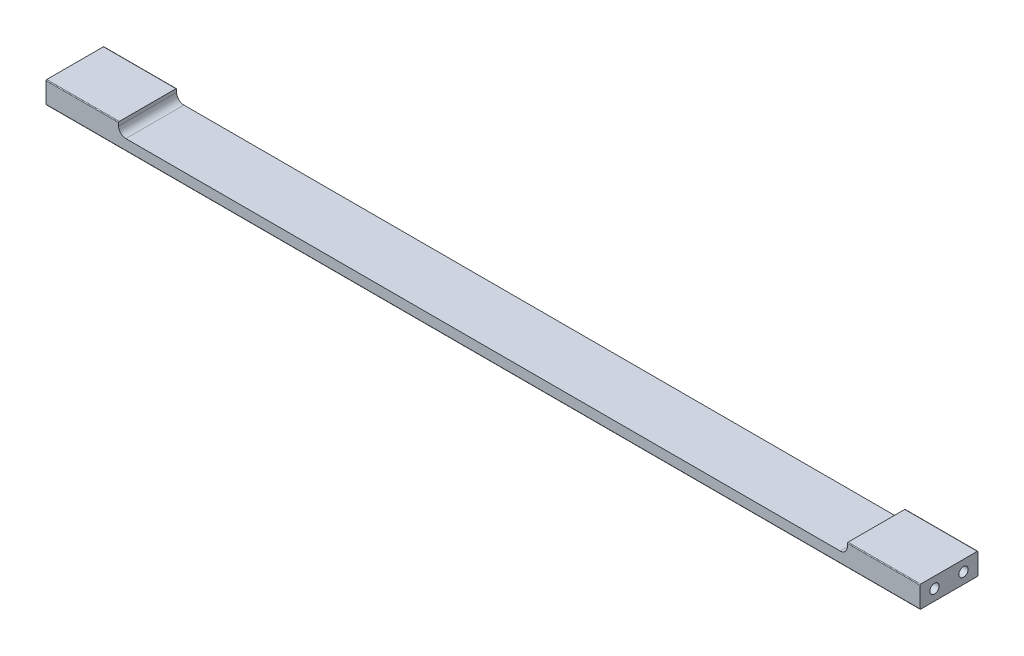
SolidWorks part; units mm, degrees
ref_plane "Front Plane" through (0, 0, 0) normal (0, 0, 1) x (1, 0, 0)
ref_plane "Top Plane" through (0, 0, 0) normal (0, 1, 0) x (1, 0, 0)
ref_plane "Right Plane" through (0, 0, 0) normal (1, 0, 0) x (0, 0, -1)
sketch "Sketch1" plane through (0, 0, 0) normal (0, 1, 0) x (1, 0, 0)
  line L1 (191.135, -12.7) -> (-191.135, -12.7)
  line L2 (191.135, -12.7) -> (191.135, 12.7)
  line L3 (191.135, 12.7) -> (-191.135, 12.7)
  line L4 (-191.135, -12.7) -> (-191.135, 12.7)
  line L5 (191.135, -12.7) -> (-191.135, 12.7) construction
  line L6 (191.135, 12.7) -> (-191.135, -12.7) construction
  point P0 (0, 0)
  dimension "Length" = 382.27
  dimension "Width" = 25.4
sketch "Sketch2" plane through (0, 0, 0) normal (1, 0, 0) x (0, 0, -1)
  line L0 (12.7, 4.7625) -> (12.7, -4.7625) construction
  point P2 (12.7, 0)
  dimension "Thickness" = 9.525
sketch "Sketch3" plane through (0, 0, 0) normal (0, 1, 0) x (1, 0, 0)
  line L1 (-191.135, 12.7) -> (191.135, 12.7)
  line L2 (-191.135, 12.7) -> (-191.135, -12.7)
  line L3 (-191.135, -12.7) -> (191.135, -12.7)
  line L4 (191.135, 12.7) -> (191.135, -12.7)
extrude "Boss-Extrude1" add sketch "Sketch3" against normal up to vertex (4.7625 mm away) and the other way up to vertex (4.7625 mm away) up to point (0, -4.7625, -12.7) other way up to point (0, 4.7625, -12.7)
fillet "Fillet1" radius 0.3143 4 edges at (0, -4.7625, 12.7) (0, -4.7625, -12.7) (0, 4.7625, -12.7) (0, 4.7625, 12.7)
sketch "Sketch4" plane through (-191.135, 0, 0) normal (-1, 0, 0) x (0, 0, 1)
  line L0 (0, 0) -> (6.35, 0) construction
  line L1 (0, 0) -> (-6.35, 0) construction
hole_wizard "Tap Drill for #10-32 Tap1" positions "Sketch5" profile "Sketch6" hole size "#10-32" standard "ANSI Inch"
sketch "Sketch5" plane through (-191.135, 0, 0) normal (-1, 0, 0) x (0, 0, 1)
  point P0 (-6.35, 0)
  point P3 (6.35, 0)
sketch "Sketch6" plane through (-191.135, 0, -6.35) normal (0, 1, 0) x (0, 0, 1)
  line L0 (0, 0) -> (0, 26.6133)
  line L1 (0, 26.6133) -> (2.0193, 25.4)
  line L2 (2.0193, 25.4) -> (2.0193, 0)
  line L5 (2.0193, 0) -> (0, 0)
  line L10 (0, 26.6133) -> (-2.0193, 25.4) construction
  line L11 (0, -6.35) -> (0, 107.95) construction
  dimension "Hole Dia." = 4.0386
  dimension "Hole Depth" = 25.4
  dimension "Drill Angle" = 118
hole_wizard "Tap Drill for #10-32 Tap2" positions "Sketch7" profile "Sketch8" hole size "#10-32" standard "ANSI Inch"
sketch "Sketch7" plane through (191.135, 0, 0) normal (1, 0, 0) x (0, 0, -1)
  point P0 (-6.35, 0)
  point P3 (6.35, 0)
sketch "Sketch8" plane through (191.135, 0, 6.35) normal (0, 1, 0) x (0, 0, -1)
  line L0 (0, 0) -> (0, 26.6133)
  line L1 (0, 26.6133) -> (2.0193, 25.4)
  line L2 (2.0193, 25.4) -> (2.0193, 0)
  line L5 (2.0193, 0) -> (0, 0)
  line L10 (0, 26.6133) -> (-2.0193, 25.4) construction
  line L11 (0, -6.35) -> (0, 107.95) construction
  dimension "Hole Dia." = 4.0386
  dimension "Hole Depth" = 25.4
  dimension "Drill Angle" = 118
sketch "Sketch9" plane through (0, 0, -12.7) normal (0, 0, -1) x (-1, 0, 0)
  line L0 (159.385, 4.7625) -> (159.385, 3.175)
  line L7 (-191.135, 4.7625) -> (191.135, 4.7625) construction
  line L8 (156.21, 0) -> (-156.21, 0)
  line L9 (-159.385, 3.175) -> (-159.385, 4.7625)
  line L10 (-159.385, 4.7625) -> (159.385, 4.7625)
  line L11 (191.135, 113.2887) -> (191.135, 38.2468) construction
  line L12 (-191.135, 113.2887) -> (-191.135, 38.2468) construction
  arc A0 (159.385, 3.175) -> (156.21, 0) centre (156.21, 3.175) cw
  arc A1 (-156.21, 0) -> (-159.385, 3.175) centre (-156.21, 3.175) cw
  point P15 (159.385, 0)
  point P18 (-159.385, 0)
  dimension "D4" = 3.175
  dimension "D1" = 31.75
  dimension "D2" = 31.75
  dimension "D3" = 4.7625
extrude "Cut-Extrude1" cut sketch "Sketch9" against normal through all
equation "\"D1@Fillet1\" = \"Thickness@Sketch2\" * .033"
